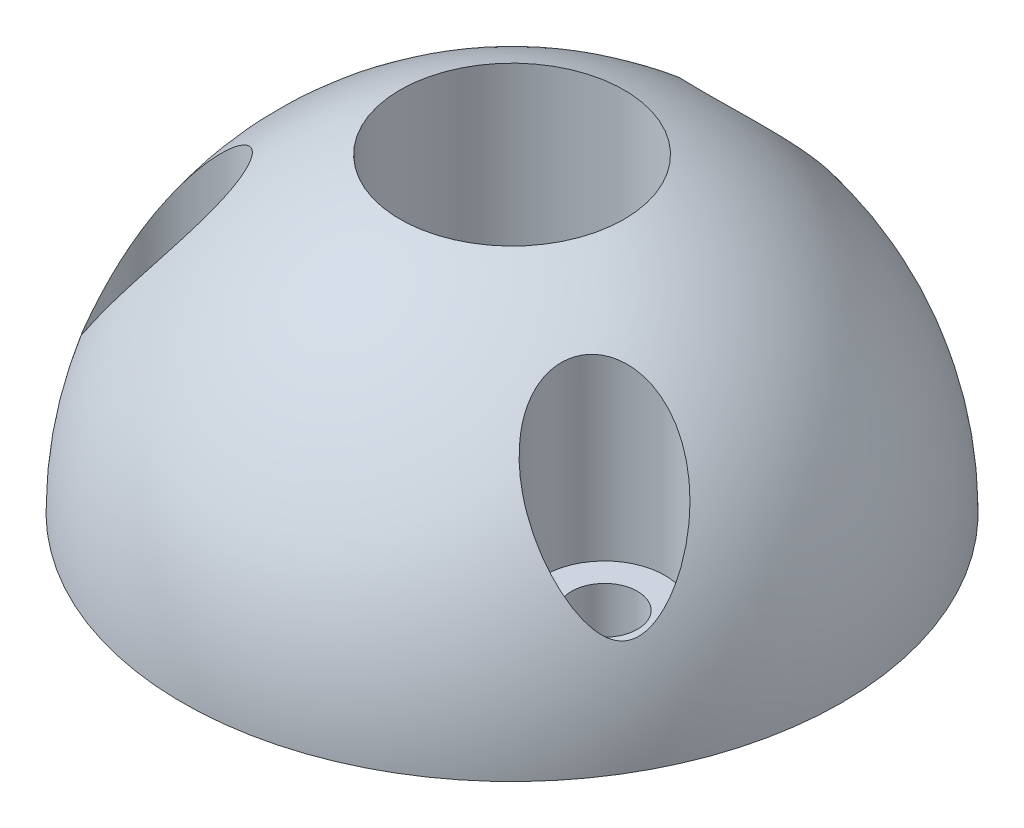
SolidWorks part; units mm, degrees
ref_plane "Front Plane" through (0, 0, 0) normal (0, 0, 1) x (1, 0, 0)
ref_plane "Top Plane" through (0, 0, 0) normal (0, 1, 0) x (1, 0, 0)
ref_plane "Right Plane" through (0, 0, 0) normal (1, 0, 0) x (0, 0, -1)
sketch "Sketch1" plane through (0, 0, 0) normal (0, 0, 1) x (1, 0, 0)
  line L0 (-15, 0) -> (15, 0)
  line L1 (0, -1000) -> (0, 49000) construction
  arc A0 (15, 0) -> (-15, 0) centre (0, 0) ccw
  dimension "D1" = 15
revolve "Revolve1" add sketch "Sketch1" angle 360 about L1 region at (-6.3662, 6.3662, 0)
sketch "Sketch2" plane through (0, 0, 0) normal (0, -1, 0) x (1, 0, 0)
  line L1 (4.8786, -8.45) -> (9.7572, 0)
  line L2 (9.7572, 0) -> (4.8786, 8.45)
  line L3 (4.8786, 8.45) -> (-4.8786, 8.45)
  line L4 (-4.8786, 8.45) -> (-9.7572, 0)
  line L5 (-9.7572, 0) -> (-4.8786, -8.45)
  line L6 (-4.8786, -8.45) -> (4.8786, -8.45)
  circle A0 centre (0, 0) radius 8.45 construction
  dimension "D1" = 16.9
extrude "Cut-Extrude2" cut sketch "Sketch2" against normal blind 3.5
sketch "Sketch3" plane through (0, 3.5, 0) normal (0, -1, 0) x (1, 0, 0)
  line L0 (-4.8786, 8.45) -> (-9.7572, 0) construction
  line L1 (3.7239, -6.45) -> (7.4478, 0)
  line L2 (7.4478, 0) -> (3.7239, 6.45)
  line L3 (3.7239, 6.45) -> (-3.7239, 6.45)
  line L4 (-3.7239, 6.45) -> (-7.4478, 0)
  line L5 (-7.4478, 0) -> (-3.7239, -6.45)
  line L6 (-3.7239, -6.45) -> (3.7239, -6.45)
  circle A0 centre (0, 0) radius 5.1
  circle A1 centre (0, 0) radius 6.45 construction
  dimension "D1" = 10.2
  dimension "D2" = 2
sketch "Sketch7" plane through (0, 0, 0) normal (0, -1, 0) x (1, 0, 0)
  line L0 (866.0254, -500) -> (-42435.2448, 24500) construction
  line L1 (-707.1068, -707.1068) -> (34648.2323, 34648.2323) construction
  line L2 (0, -1000) -> (0, 49000) construction
  circle A0 centre (-9.9593, 5.75) radius 1.5
  circle A1 centre (9.9593, 5.75) radius 1.5
  circle A2 centre (0, -11.5) radius 1.5
  point P16 (0, 0)
  dimension "D1" = 3
  dimension "D3" = 11.5
  dimension "D4" = 60
  dimension "D2" = 3
extrude "Cut-Extrude6" cut sketch "Sketch7" against normal blind 7
extrude "Cut-Extrude7" cut sketch "Sketch3" against normal through all contours A0 region at (0, 3.5, 0)
sketch "Sketch8" plane through (0, 0, 0) normal (0, 1, 0) x (1, 0, 0)
  circle A3 centre (-9.9593, -5.75) radius 2.75
  circle A4 centre (0, 11.5) radius 2.75
  circle A5 centre (9.9593, -5.75) radius 2.75
  point P9 (0, 0)
  point P12 (0, 0)
  dimension "D2" = 3
  dimension "D1" = 5.5
extrude "Cut-Extrude8" cut sketch "Sketch8" along normal through all from offset 4
